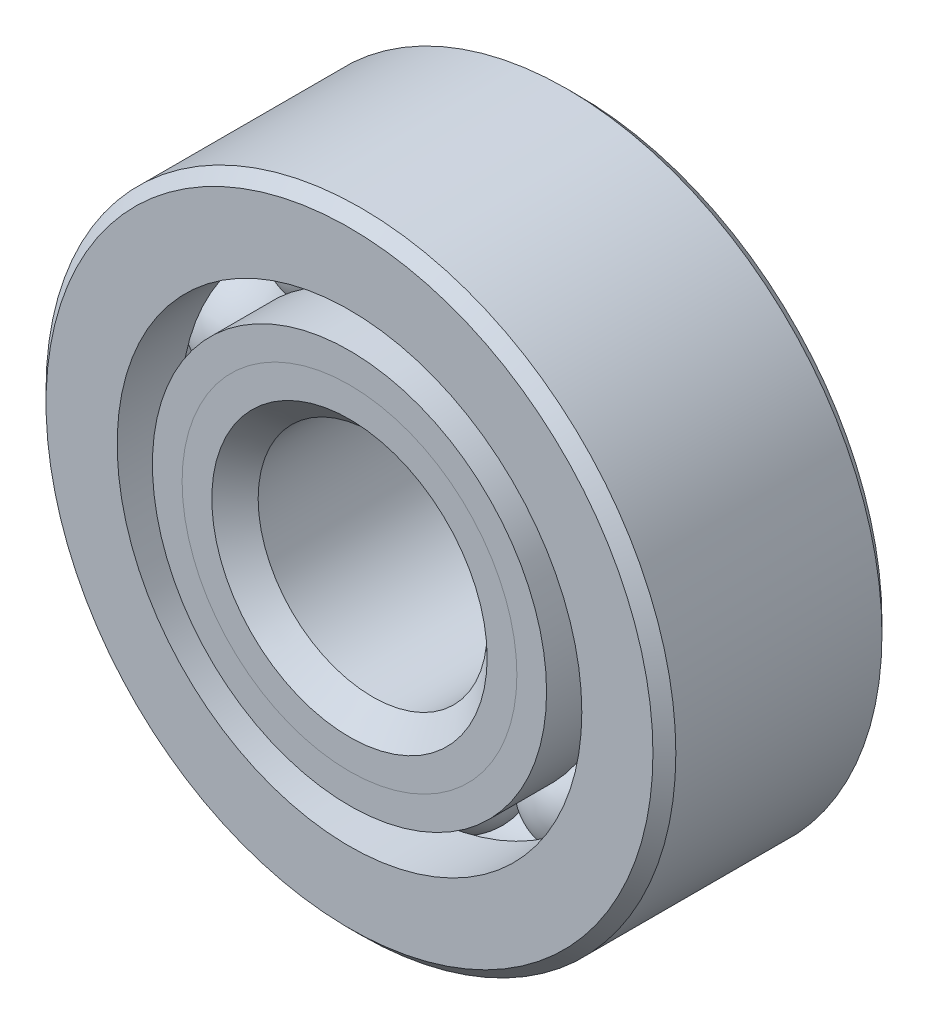
SolidWorks part; units mm, degrees
ref_plane "Front Plane" through (0, 0, 0) normal (0, 0, 1) x (1, 0, 0)
ref_plane "Top Plane" through (0, 0, 0) normal (0, 1, 0) x (1, 0, 0)
ref_plane "Right Plane" through (0, 0, 0) normal (1, 0, 0) x (0, 0, -1)
sketch "Sketch1" plane through (0, 0, 0) normal (1, 0, 0) x (0, 0, -1)
  line L0 (-3.175, 0) -> (3.175, 0) construction
  line L1 (0, 8.7312) -> (0, -8.7312) construction
  line L2 (2.8575, 8.7312) -> (-2.8575, 8.7312)
  line L3 (-2.8575, 8.7312) -> (-3.175, 8.4137)
  line L4 (-3.175, 8.4137) -> (-3.175, 6.4416)
  line L5 (-3.175, 6.4416) -> (-1.4111, 6.4416)
  line L6 (3.175, 6.4416) -> (1.4111, 6.4416)
  line L7 (3.175, 8.4137) -> (3.175, 6.4416)
  line L8 (2.8575, 8.7312) -> (3.175, 8.4137)
  line L9 (0, 8.7312) -> (0, 5.9531) construction
  line L10 (0, 5.9531) -> (0, 3.175) construction
  arc A0 (-1.4111, 6.4416) -> (1.4111, 6.4416) centre (0, 5.9531) cw
  point P14 (0, 3.175)
  dimension "D3" = 2.8222
  dimension "D1" = 45
  dimension "Width" = 6.35
  dimension "OD" = 17.4625
  dimension "D2" = 0.3175
  dimension "Shaft Dia" = 6.35
  dimension "D4" = 0.4885
revolve "Revolve1" add sketch "Sketch1" angle 360 about L0
sketch "Sketch2" plane through (0, 0, 0) normal (1, 0, 0) x (0, 0, -1)
  line L0 (-3.175, 5.4647) -> (-1.4111, 5.4647)
  line L1 (-3.175, 8.4137) -> (-3.175, -8.4137) construction
  line L2 (-3.175, 5.4647) -> (-3.175, 4.641)
  line L3 (-3.175, 4.641) -> (-2.3514, 3.8174)
  line L4 (-2.3514, 3.8174) -> (0, 3.8174)
  line L5 (0, 8.7312) -> (0, -8.7312) construction
  line L6 (0, 3.8174) -> (0, 4.4599)
  line L7 (0, 4.4599) -> (0, 3.175) construction
  line L8 (-3.175, 5.4647) -> (-3.175, 3.8174) construction
  line L9 (-3.175, 3.8174) -> (-2.3514, 3.8174) construction
  arc A0 (-1.4111, 5.4647) -> (0, 4.4599) centre (0, 5.9531) ccw
  arc A1 (1.4111, 6.4416) -> (-1.4111, 6.4416) centre (0, 5.9531) ccw construction
  circle A2 centre (0, 5.9531) radius 1.4933 construction
  dimension "D1" = 45
revolve "Revolve2" add sketch "Sketch2" angle 360 about L0
sketch "Sketch3" plane through (0, 0, 0) normal (1, 0, 0) x (0, 0, -1)
  line L0 (-3.175, 4.641) -> (-2.3514, 3.8174)
  line L1 (-2.3514, 3.8174) -> (0, 3.8174)
  line L2 (0, 3.8174) -> (0, 4.4599)
  line L3 (-3.175, 4.641) -> (-3.175, 3.8174)
  line L4 (-3.175, 5.4647) -> (-3.175, 3.8174) construction
  line L5 (-3.175, 3.8174) -> (-2.5326, 3.175)
  line L6 (-2.5326, 3.175) -> (2.8575, 3.175)
  line L7 (2.8575, 8.7312) -> (2.8575, -8.7312) construction
  line L8 (2.8575, 3.175) -> (3.175, 3.4925)
  line L9 (3.175, -8.4137) -> (3.175, 8.4137) construction
  line L10 (3.175, 3.4925) -> (3.175, 5.4647)
  line L11 (3.175, 5.4647) -> (1.4111, 5.4647)
  line L13 (2.8575, 8.7312) -> (3.175, 8.4137) construction
  circle A0 centre (0, 5.9531) radius 1.4933 construction
  arc A1 (1.4111, 5.4647) -> (0, 4.4599) centre (0, 5.9531) cw
revolve "Revolve3" add sketch "Sketch3" angle 360 about L0
sketch "Sketch4" plane through (0, 0, 0) normal (1, 0, 0) x (0, 0, -1)
  line L0 (-1.4933, 5.9531) -> (1.4933, 5.9531)
  circle A1 centre (0, 5.9531) radius 1.4933 construction
  arc A2 (-1.4933, 5.9531) -> (1.4933, 5.9531) centre (0, 5.9531) cw
  arc A3 (1.4111, 6.4416) -> (-1.4111, 6.4416) centre (0, 5.9531) ccw construction
revolve "Revolve4" add sketch "Sketch4" angle 360 about L0
ref_axis "Axis1" through (0, 0, -3.175) along (0, 0, 1)
pattern_circular "CirPattern1" count 10 every 36 about axis through (0, 0, -3.175) along (0, 0, 1) of bodies 104
equation "\"D2@Sketch1\" = \"Width@Sketch1\"*.05"
equation "\"D3@Sketch1\" = \"Width@Sketch1\"/2.25"
equation "\"D4@Sketch1\" = (((\"OD@Sketch1\"-\"Width@Sketch1\")/2)/3.25)/3.5"
equation "\"D2@CirPattern1\" = 360/\"Balls@CirPattern1\""
